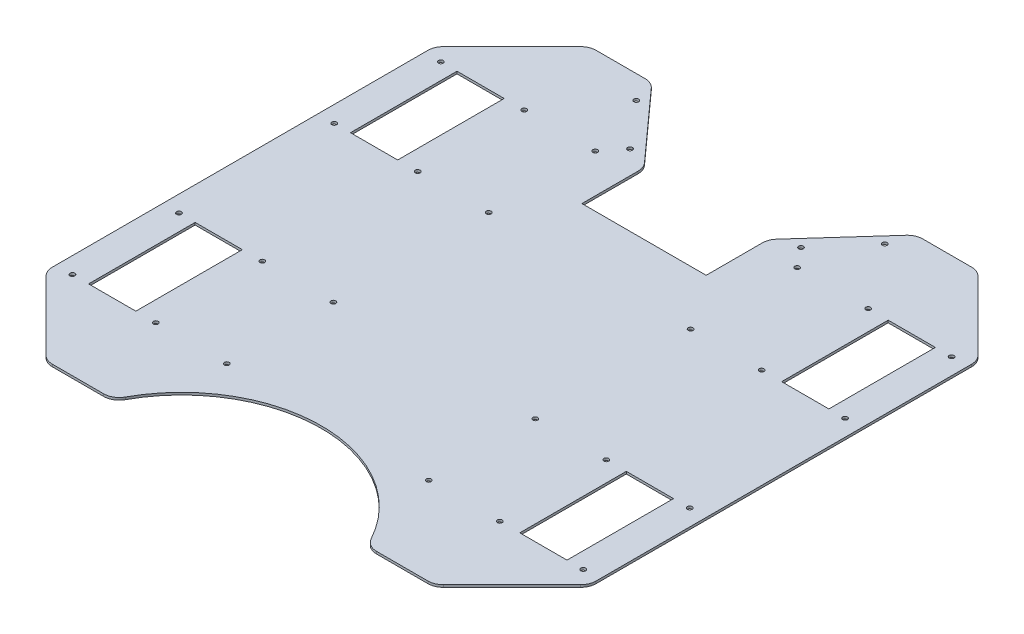
SolidWorks part; units mm, degrees
material "PMMA"
ref_plane "前视基准面" through (0, 0, 0) normal (0, 0, 1) x (1, 0, 0)
ref_plane "上视基准面" through (0, 0, 0) normal (0, 1, 0) x (1, 0, 0)
ref_plane "右视基准面" through (0, 0, 0) normal (1, 0, 0) x (0, 0, -1)
other "Configuration Table"
sketch "草图1" plane through (0, 0, 0) normal (0, 1, 0) x (1, 0, 0)
  line L0 (-125, 175) -> (-175, 125)
  line L1 (125, -175) -> (81.7103, -175)
  line L2 (175, -125) -> (175, 125)
  line L3 (125, 175) -> (85, 175)
  line L4 (-175, -125) -> (-175, 125)
  line L5 (-85, 175) -> (-40, 125)
  line L7 (125, 175) -> (175, 125)
  line L8 (175, -125) -> (125, -175)
  line L9 (-125, -175) -> (-175, -125)
  line L10 (40, 125) -> (85, 175)
  line L11 (-85, 175) -> (-125, 175)
  line L12 (40, 125) -> (40, 85)
  line L13 (40, 85) -> (-40, 85)
  line L14 (-40, 85) -> (-40, 125)
  line L15 (-153.994, 50) -> (-123.594, 50)
  line L16 (-123.594, 50) -> (-123.594, 118.58)
  line L17 (-123.594, 118.58) -> (-153.994, 118.58)
  line L18 (-153.994, 118.58) -> (-153.994, 50)
  line L19 (123.594, 50) -> (153.994, 50)
  line L20 (153.994, 50) -> (153.994, 118.58)
  line L21 (153.994, 118.58) -> (123.594, 118.58)
  line L22 (123.594, 118.58) -> (123.594, 50)
  line L23 (-175, 0) -> (175, 0) construction
  line L24 (-123.594, -118.58) -> (-153.994, -118.58)
  line L25 (-123.594, -50) -> (-123.594, -118.58)
  line L26 (-153.994, -50) -> (-123.594, -50)
  line L27 (-153.994, -118.58) -> (-153.994, -50)
  line L28 (153.994, -118.58) -> (123.594, -118.58)
  line L29 (153.994, -50) -> (153.994, -118.58)
  line L30 (123.594, -50) -> (153.994, -50)
  line L31 (123.594, -118.58) -> (123.594, -50)
  line L32 (-81.7103, -175) -> (-125, -175)
  line L33 (-80, 160) -> (-55, 131) construction
  circle A0 centre (-55, 131) radius 1.55
  circle A1 centre (-80, 160) radius 1.55
  circle A2 centre (55, 131) radius 1.55
  circle A3 centre (80, 160) radius 1.55
  circle A4 centre (-65, 118.58) radius 1.55
  circle A5 centre (-65, 50) radius 1.55
  circle A6 centre (-110.72, 50) radius 1.55
  circle A7 centre (-110.72, 118.58) radius 1.55
  circle A12 centre (-164.434, 118.58) radius 1.55
  circle A13 centre (-164.434, 50) radius 1.55
  circle A14 centre (-65, -118.58) radius 1.55
  circle A15 centre (-65, -50) radius 1.55
  circle A16 centre (-110.72, -50) radius 1.55
  circle A17 centre (-110.72, -118.58) radius 1.55
  circle A18 centre (-164.434, -50) radius 1.55
  circle A19 centre (-164.434, -118.58) radius 1.55
  circle A20 centre (65, 50) radius 1.55
  circle A21 centre (110.72, 50) radius 1.55
  circle A22 centre (110.72, 118.58) radius 1.55
  circle A23 centre (65, 118.58) radius 1.55
  circle A24 centre (164.434, 118.58) radius 1.55
  circle A25 centre (164.434, 50) radius 1.55
  circle A26 centre (164.434, -118.58) radius 1.55
  circle A27 centre (164.434, -50) radius 1.55
  circle A28 centre (110.72, -50) radius 1.55
  circle A29 centre (110.72, -118.58) radius 1.55
  circle A30 centre (65, -118.58) radius 1.55
  circle A31 centre (65, -50) radius 1.55
  arc A32 (-81.7103, -175) -> (81.7103, -175) centre (0, -212.7283) cw
  point P0 (0, 0)
  point P1 (-85, 175)
  point P2 (85, 175)
  point P3 (40, 125)
  point P4 (-40, 125)
  point P6 (125, 175)
  point P8 (175, 125)
  point P10 (175, -125)
  point P11 (125, -175)
  point P12 (-125, -175)
  point P13 (-175, -125)
  point P24 (-80, 160)
  point P25 (-55, 131)
  point P26 (55, 131)
  point P27 (80, 160)
  point P36 (-164.434, 118.58)
  point P37 (-164.434, 50)
  point P38 (-153.994, 118.58)
  point P39 (-123.594, 50)
  point P40 (-110.72, 118.58)
  point P41 (-110.72, 50)
  point P42 (-65, 118.58)
  point P43 (-65, 50)
  point P47 (-123.594, 118.58)
  point P53 (-153.994, 50)
  point P66 (-40, 85)
  point P67 (40, 85)
  point P70 (110.72, 50)
  point P71 (65, 50)
  point P72 (123.594, 50)
  point P73 (153.994, 50)
  point P74 (164.434, 50)
  point P75 (65, 118.58)
  point P76 (110.72, 118.58)
  point P77 (123.594, 118.58)
  point P78 (153.994, 118.58)
  point P81 (164.434, 118.58)
  point P85 (-65, -118.58)
  point P88 (-65, -50)
  point P91 (-110.72, -50)
  point P94 (-110.72, -118.58)
  point P101 (-164.434, -50)
  point P104 (-164.434, -118.58)
  point P118 (164.434, -118.58)
  point P121 (164.434, -50)
  point P128 (110.72, -50)
  point P131 (110.72, -118.58)
  point P134 (65, -118.58)
  point P137 (65, -50)
  dimension "D29" = 3.1
  dimension "D30" = 3.1
  dimension "D31" = 3.1
  dimension "D32" = 3.1
  dimension "D40" = 3.1
  dimension "D41" = 3.1
  dimension "D42" = 3.1
  dimension "D43" = 3.1
  dimension "D44" = 3.1
  dimension "D45" = 3.1
  dimension "D46" = 3.1
  dimension "D47" = 3.1
  dimension "D48" = 3.1
  dimension "D49" = 3.1
  dimension "D60" = 3.1
  dimension "D61" = 3.1
  dimension "D62" = 43.2897
  dimension "D63" = 90
  dimension "D1" = 175
  dimension "D2" = 175
  dimension "D3" = 125
  dimension "D4" = 125
  dimension "D5" = 125
  dimension "D6" = 125
  dimension "D7" = 125
  dimension "D8" = 125
  dimension "D9" = 125
  dimension "D10" = 125
  dimension "D11" = 175
  dimension "D12" = 175
  dimension "D13" = 40
  dimension "D14" = 40
  dimension "D15" = 85
  dimension "D16" = 85
  dimension "D17" = 125
  dimension "D18" = 125
  dimension "D19" = 40
  dimension "D20" = 45
  dimension "D21" = 160
  dimension "D22" = 160
  dimension "D23" = 80
  dimension "D24" = 80
  dimension "D25" = 55
  dimension "D26" = 131
  dimension "D27" = 55
  dimension "D28" = 131
  dimension "D33" = 50
  dimension "D34" = 118.58
  dimension "D35" = 65
  dimension "D36" = 45.72
  dimension "D37" = 12.874
  dimension "D38" = 30.4
  dimension "D39" = 10.44
  dimension "D50" = 40
  dimension "D51" = 40
  dimension "D52" = 85
  dimension "D53" = 85
  dimension "D54" = 138.013
  dimension "D55" = 65
  dimension "D56" = 45.72
  dimension "D57" = 12.874
  dimension "D58" = 30.4
  dimension "D59" = 10.44
  dimension "D64" = 0
extrude "凸台-拉伸1" add sketch "草图1" along normal blind 1.5 contours A1 | A0 | L8 L1 A32 L32 L9 L4 L0 L11 L5 L14 L13 L12 L10 L3 L7 L2 | A5 | A3 | A2 | A4 | A7 | A12 | L16 L17 L18 L15 | A6 | L21 L22 L19 L20 | A13 | A16 | A17 | A14 | A15 | A18 | A19 | L25 L24 L27 L26 | A20 | A21 | A22 | A23 | A24 | A25 | A28 | A26 | A27 | L28 L31 L30 L29 | A30 | A31 | A29
fillet "圆角1" radius 10 1 edges at (-40, 0.75, -125)
fillet "圆角2" radius 10 1 edges at (40, 0.75, -125)
fillet "圆角3" radius 10 12 edges at (-85, 0.75, -175) (85, 0.75, -175) (125, 0.75, -175) (175, 0.75, -125) (175, 0.75, 125) (125, 0.75, 175) (81.7103, 0.75, 175) (-81.7103, 0.75, 175) (-125, 0.75, 175) (-175, 0.75, 125) (-175, 0.75, -125) (-125, 0.75, -175)
